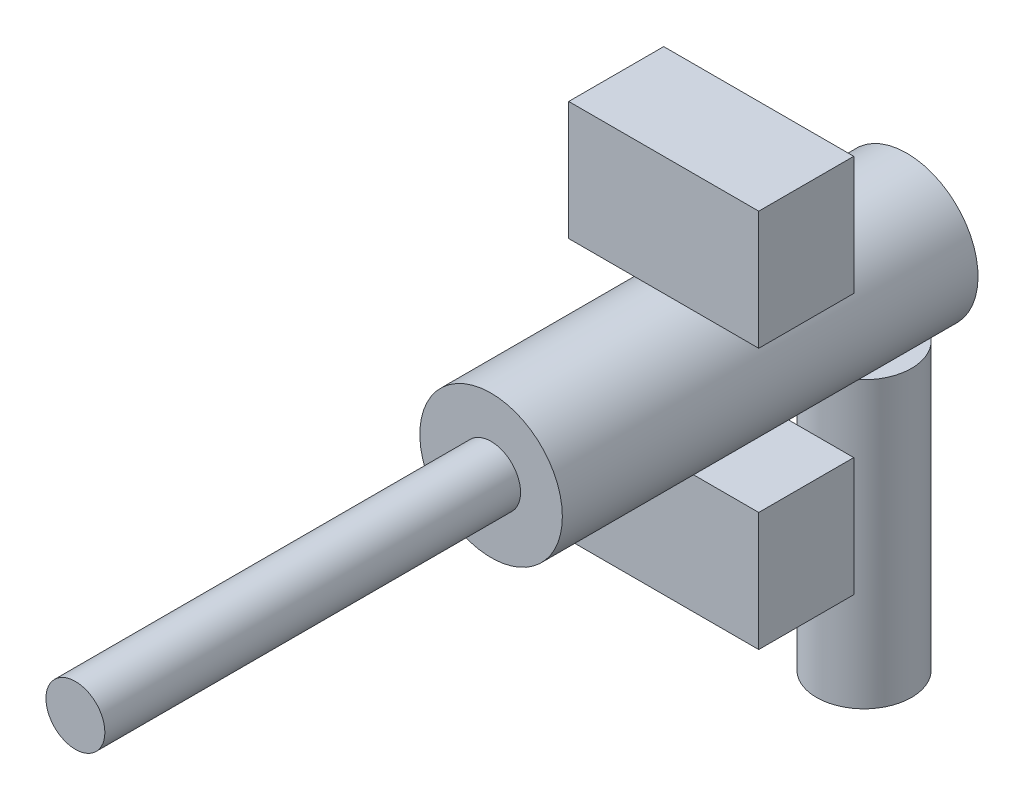
SolidWorks part; units mm, degrees
ref_plane "Front Plane" through (0, 0, 0) normal (0, 0, 1) x (1, 0, 0)
ref_plane "Top Plane" through (0, 0, 0) normal (0, 1, 0) x (1, 0, 0)
ref_plane "Right Plane" through (0, 0, 0) normal (1, 0, 0) x (0, 0, -1)
sketch "Sketch1" plane through (0, 0, 17.9882) normal (0, 1, 0) x (1, 0, 0)
  circle A0 centre (0, 0) radius 20
  dimension "D1" = 40
extrude "Boss-Extrude1" add sketch "Sketch1" along normal blind 120
sketch "Sketch2" plane through (0, 0, 0) normal (0, 0, 1) x (1, 0, 0)
  circle A0 centre (0, 149.4875) radius 30
  dimension "D1" = 60
extrude "Boss-Extrude2" add sketch "Sketch2" along normal blind 175
sketch "Sketch3" plane through (0, 0, 175) normal (0, 0, 1) x (1, 0, 0)
  circle A0 centre (0, 149.4875) radius 12.4009
extrude "Boss-Extrude3" add sketch "Sketch3" along normal blind 175
sketch "Sketch4" plane through (0, 0, 0) normal (1, 0, 0) x (0, 0, -1)
  line L0 (0, 179.4875) -> (-175, 179.4875) construction
  line L5 (-102.3218, 119.6417) -> (-62.3218, 119.6417)
  line L6 (-102.3218, 119.6417) -> (-102.3218, 69.6417)
  line L7 (-102.3218, 69.6417) -> (-62.3218, 69.6417)
  line L8 (-62.3218, 119.6417) -> (-62.3218, 69.6417)
  line L9 (-102.3218, 179.4875) -> (-62.3218, 179.4875)
  line L10 (-102.3218, 179.4875) -> (-102.3218, 229.4875)
  line L11 (-102.3218, 229.4875) -> (-62.3218, 229.4875)
  line L12 (-62.3218, 179.4875) -> (-62.3218, 229.4875)
  dimension "D1" = 50
  dimension "D2" = 50
  dimension "D3" = 40
  dimension "D4" = 40
extrude "Boss-Extrude4" add sketch "Sketch4" along normal blind 40 and the other way blind 40
